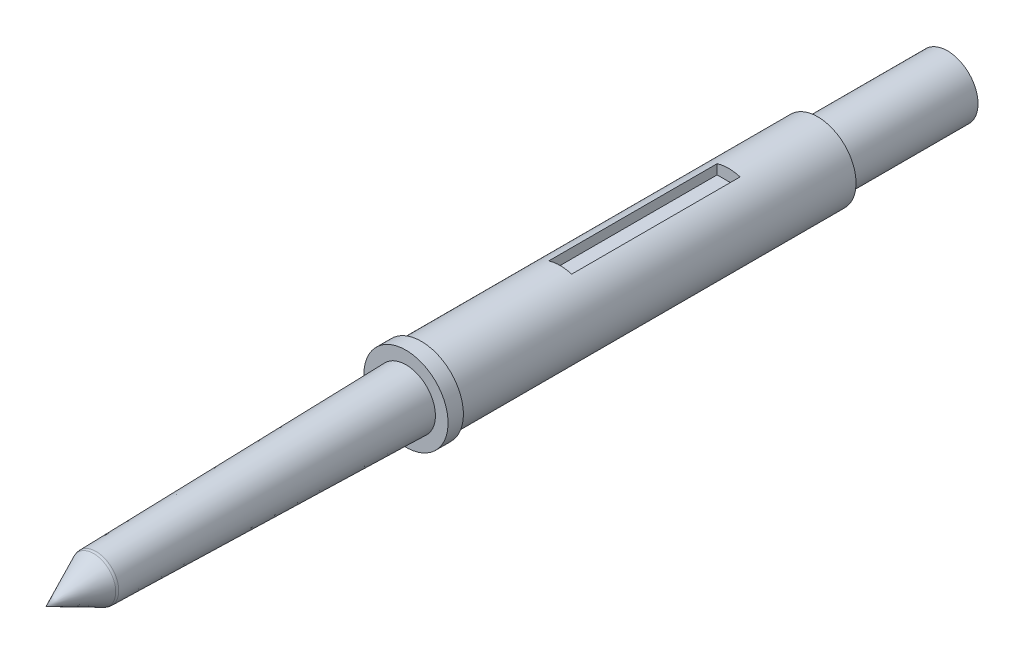
SolidWorks part; units mm, degrees
ref_plane "Front Plane" through (0, 0, 0) normal (0, 0, 1) x (1, 0, 0)
ref_plane "Top Plane" through (0, 0, 0) normal (0, 1, 0) x (1, 0, 0)
ref_plane "Right Plane" through (0, 0, 0) normal (1, 0, 0) x (0, 0, -1)
sketch "Sketch3" plane through (0, 0, 0) normal (1, 0, 0) x (0, 0, -1)
  line L0 (0, 0) -> (-259.5858, 0) construction
  line L4 (-177.8, 0) -> (0, 0)
  line L6 (-176.5581, 4.6891) -> (-112.3, 6.1099)
  line L7 (-112.3, 6.1099) -> (-112.3, 8.7312)
  line L8 (-112.3, 8.7312) -> (-109.125, 8.7312)
  line L11 (-26.8925, 7.9375) -> (-26.8925, 6.35)
  line L12 (-26.8925, 6.35) -> (0, 6.35)
  line L13 (0, 6.35) -> (0, 0)
  line L15 (-115.8, 6.0325) -> (-115.8, 0) construction
  line L16 (-112.3, 6.1099) -> (-168.6233, 6.1099) construction
  line L22 (-177.8, 3.4195) -> (-177.8, 0) construction
  line L23 (-177.0628, 4.5723) -> (-186.9554, 0)
  line L24 (-186.9554, 0) -> (-177.8, 0)
  line L26 (-26.8925, 16.9069) -> (-26.8925, -16.9069) construction
  line L30 (-109.125, 8.7312) -> (-109.125, 7.9375)
  line L32 (-109.125, 7.9375) -> (-26.8925, 7.9375)
  arc A0 (-177.8, 3.4195) -> (-176.5581, 4.6891) centre (-176.53, 3.4195) cw
  point P3 (-115.8, 6.0325)
  point P5 (-177.8, 4.6617)
  dimension "D2" = 65.5
  dimension "D9" = 1.27
  dimension "D3" = 17.4625
  dimension "D4" = 12.7
  dimension "D5" = 15.875
  dimension "D6" = 177.8
  dimension "D7" = 3.175
  dimension "D10" = 3.5
  dimension "D11" = 12.065
  dimension "D13" = 1.267
revolve "Revolve2" add sketch "Sketch3" angle 360 about L0 region at (0, 3.463, 84.9232)
ref_plane "Plane1" through (0, 7.9375, 0) normal (0, 1, 0) x (1, 0, 0)
sketch "Sketch4" plane through (0, 7.9375, 0) normal (0, 1, 0) x (1, 0, 0)
  line L0 (0, 0) -> (0, -62.8551) construction
  line L1 (2.3813, -80.3176) -> (-2.3812, -80.3176)
  line L2 (2.3813, -80.3176) -> (2.3813, -45.3926)
  line L3 (2.3813, -45.3926) -> (-2.3812, -45.3926)
  line L4 (-2.3812, -80.3176) -> (-2.3812, -45.3926)
  line L5 (2.3813, -80.3176) -> (-2.3812, -45.3926) construction
  line L6 (2.3813, -45.3926) -> (-2.3812, -80.3176) construction
  point P0 (0, -62.8551)
  dimension "D1" = 34.925
  dimension "D2" = 4.7625
extrude "Cut-Extrude1" cut sketch "Sketch4" against normal blind 2.3813
